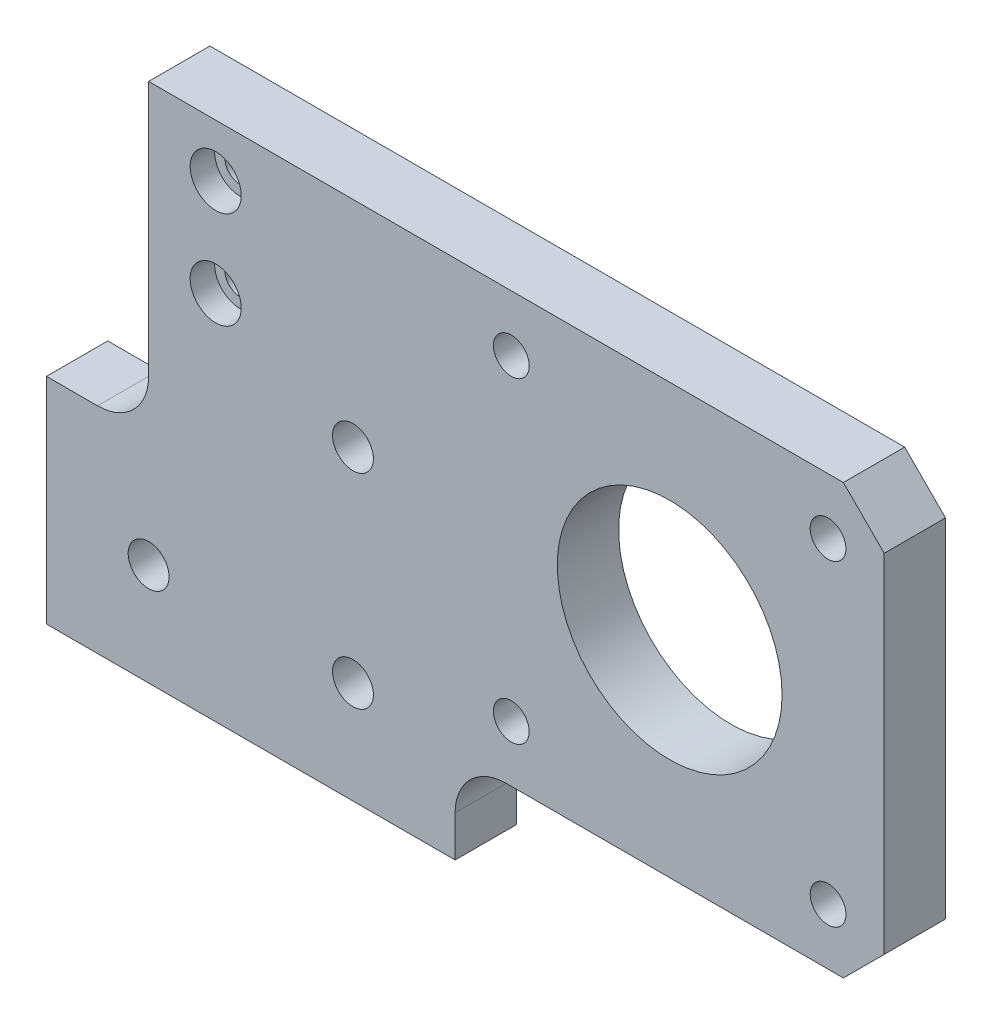
SolidWorks part; units mm, degrees
ref_plane "Plano frontal" through (0, 0, 0) normal (0, 0, 1) x (1, 0, 0)
ref_plane "Plano superior" through (0, 0, 0) normal (0, 1, 0) x (1, 0, 0)
ref_plane "Plano direito" through (0, 0, 0) normal (1, 0, 0) x (0, 0, -1)
sketch "Esboço1" plane through (0, 0, 0) normal (0, 0, 1) x (1, 0, 0)
  line L0 (30, 0) -> (30, 51) construction
  line L1 (0, 0) -> (40, 0)
  line L2 (0, 0) -> (0, 51)
  line L3 (0, 51) -> (40, 51)
  line L4 (40, 0) -> (40, 51)
  line L5 (40, 9) -> (82, 9)
  line L6 (40, 9) -> (40, 51)
  line L7 (40, 51) -> (82, 51)
  line L8 (82, 9) -> (82, 51)
  line L9 (45.5, 45.5) -> (76.5, 45.5) construction
  line L10 (45.5, 45.5) -> (45.5, 14.5) construction
  line L11 (45.5, 14.5) -> (76.5, 14.5) construction
  line L12 (76.5, 45.5) -> (76.5, 14.5) construction
  line L13 (45.5, 45.5) -> (76.5, 14.5) construction
  line L14 (45.5, 14.5) -> (76.5, 45.5) construction
  line L15 (0, 10) -> (40, 10) construction
  line L16 (10, 0) -> (10, 51) construction
  line L17 (0, 30) -> (40, 30) construction
  line L18 (61, 51) -> (61, 9) construction
  line L19 (82, 30) -> (61, 30) construction
  circle A0 centre (45.5, 45.5) radius 1.75
  circle A1 centre (76.5, 45.5) radius 1.75
  circle A2 centre (76.5, 14.5) radius 1.75
  circle A3 centre (45.5, 14.5) radius 1.75
  circle A4 centre (61, 30) radius 11
  circle A5 centre (30, 10) radius 2
  circle A6 centre (10, 10) radius 2
  circle A7 centre (30, 30) radius 2
  point P9 (82, 30)
  point P10 (61, 30)
  dimension "D5" = 3.5
  dimension "D6" = 22
  dimension "D11" = 4
  dimension "D2" = 40
  dimension "D3" = 42
  dimension "D4" = 30
  dimension "D12" = 31
  dimension "D10" = 20
  dimension "D7" = 10
  dimension "D8" = 10
  dimension "D9" = 20
extrude "Ressalto-extrusão1" add sketch "Esboço1" along normal blind 6 contours L1 L4 L3 L2 A7 A6 A5 | L5 L8 L7 L6 L4 A4 A3 A2 A1 A0 region at (19.9372, 25.6663, 0) region at (40.594, 30, 0)
chamfer "Chanfro1" distance 4 angle 45 2 edges at (82, 9, 3) (82, 51, 3)
sketch "Esboço2" plane through (0, 0, 0) normal (0, 0, -1) x (-1, 0, 0)
  line L1 (0, 51) -> (-10, 51)
  line L2 (0, 51) -> (0, 21)
  line L3 (0, 21) -> (-10, 21)
  line L4 (-10, 51) -> (-10, 21)
  dimension "D1" = 30
  dimension "D2" = 10
extrude "Corte-extrusão1" cut sketch "Esboço2" against normal up to surface (6 mm away) up to face at (32, 30, 6)
fillet "Filete2" radius 5 2 edges at (40, 9, 3) (10, 21, 3)
sketch "Esboço5" plane through (0, 0, 0) normal (0, 0, -1) x (-1, 0, 0)
  circle A0 centre (-16.5625, 36.3125) radius 1.175 construction
  circle A1 centre (-16.5625, 45.8375) radius 1.175 construction
  circle A2 centre (-16.5625, 36.3125) radius 1.175 construction
  circle A3 centre (-16.5625, 45.8375) radius 1.175 construction
  circle A4 centre (-16.5625, 45.8375) radius 1.5
  circle A5 centre (-16.5625, 36.3125) radius 1.5
  dimension "D1" = 3
extrude "Corte-extrusão3" cut sketch "Esboço5" against normal up to surface (6 mm away) up to face at (39.1667, 21, 6)
sketch "Esboço6" plane through (0, 0, 6) normal (0, 0, 1) x (1, 0, 0)
  circle A0 centre (16.5625, 45.8375) radius 2.5
  circle A1 centre (16.5625, 36.3125) radius 2.5
  dimension "D1" = 5
extrude "Corte-extrusão4" cut sketch "Esboço6" against normal blind 2.4
